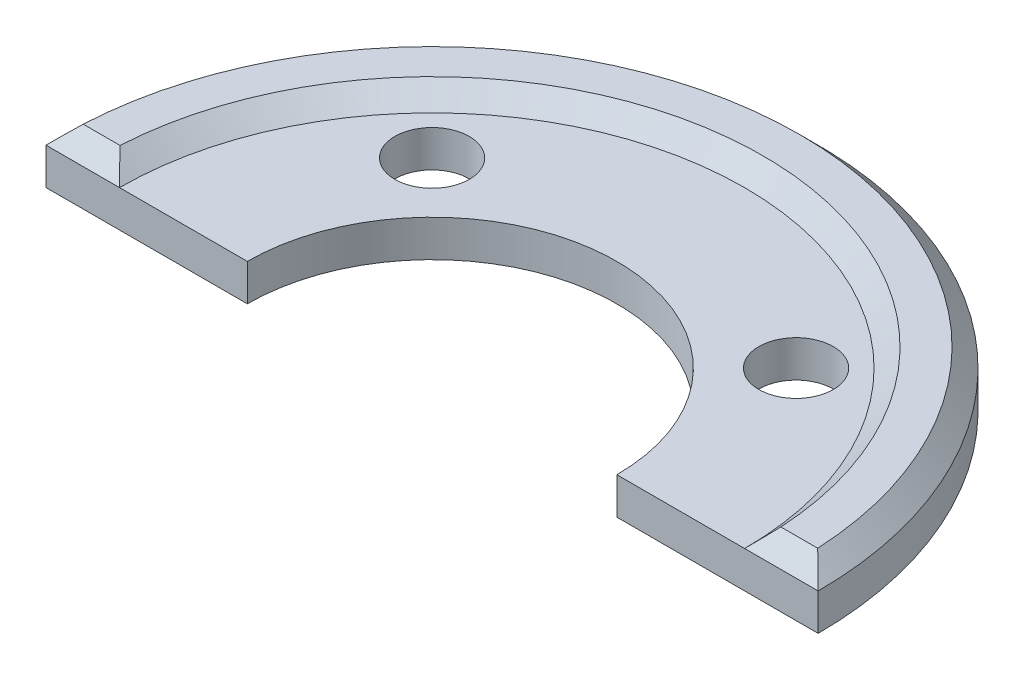
SolidWorks part; units mm, degrees
material "ABS"
ref_plane "正面" through (0, 0, 0) normal (0, 0, 1) x (1, 0, 0)
ref_plane "平面" through (0, 0, 0) normal (0, 1, 0) x (1, 0, 0)
ref_plane "右側面" through (0, 0, 0) normal (1, 0, 0) x (0, 0, -1)
sketch "ｽｹｯﾁ1" plane through (0, 0, 0) normal (0, 1, 0) x (1, 0, 0)
  line L0 (-10.05, 0) -> (-39, 0)
  line L1 (-39, 0) -> (-47.5, 8.5)
  line L2 (-47.5, 8.5) -> (-47.5, 58)
  line L3 (-47.5, 58) -> (47.5, 58)
  line L4 (47.5, 58) -> (47.5, 8.5)
  line L5 (47.5, 8.5) -> (39, 0)
  line L6 (39, 0) -> (10.05, 0)
  line L7 (-10.05, 0) -> (0, 0) construction
  line L8 (0, 0) -> (10.05, 0) construction
  arc A0 (10.05, 0) -> (-10.05, 0) centre (0, 0) ccw
  dimension "D1" = 20.1
  dimension "D2" = 95
  dimension "D3" = 58
  dimension "D4" = 78
extrude "ﾎﾞｽ - 押し出し1" add sketch "ｽｹｯﾁ1" along normal blind 3
hole_wizard "M2 なべ頭ねじ用座ぐり穴1" positions "ｽｹｯﾁ2" profile "ｽｹｯﾁ3" counterbore size "M2" standard "ISO"
sketch "ｽｹｯﾁ2" plane through (0, 3, 0) normal (0, 1, 0) x (1, 0, 0)
  line L0 (-43.5, 54) -> (-22.5, 54) construction
  line L2 (47.5, 58) -> (-47.5, 58) construction
  line L3 (-47.5, 58) -> (-47.5, 8.5) construction
  point P0 (-43.5, 54)
  point P2 (-22.5, 54)
  dimension "D1" = 4
  dimension "D2" = 4
  dimension "D3" = 21
sketch "ｽｹｯﾁ3" plane through (-43.5, 3, -54) normal (1, 0, 0) x (0, 0, 1)
  line L0 (0, 0) -> (0, 4.6309)
  line L1 (0, 4.6309) -> (1.05, 4)
  line L2 (1.05, 4) -> (1.05, 1)
  line L3 (1.05, 1) -> (2, 1)
  line L4 (2, 1) -> (2, 0)
  line L5 (2, 0) -> (0, 0)
  line L10 (0, 4.6309) -> (-1.05, 4) construction
  line L11 (0, -6.35) -> (0, 107.95) construction
  dimension "穴の直径" = 2.1
  dimension "穴の深さ" = 4
  dimension "座ぐり穴の直径" = 4
  dimension "座ぐり穴の深さ" = 1
  dimension "ﾄﾞﾘﾙ角度" = 118
pattern_linear "直線ﾊﾟﾀｰﾝ1" count 3 spacing 33 along (1, 0, 0) of "M2 なべ頭ねじ用座ぐり穴1"
pattern_linear "直線ﾊﾟﾀｰﾝ2" count 3 spacing 10.5 along (0, 0, 1) of "M2 なべ頭ねじ用座ぐり穴1", "直線ﾊﾟﾀｰﾝ1"
pattern_linear "直線ﾊﾟﾀｰﾝ3" count 2 spacing 31.5 along (0, 0, 1) of "M2 なべ頭ねじ用座ぐり穴1"
hole_wizard "M2 ねじ穴1" positions "ｽｹｯﾁ4" profile "ｽｹｯﾁ5" tap size "M2" standard "ISO"
sketch "ｽｹｯﾁ4" plane through (0, 3, 0) normal (0, 1, 0) x (1, 0, 0)
  line L0 (-22.5, 10.5) -> (-22.5, 22.5) construction
  line L1 (-22.5, 22.5) -> (-10.5, 22.5) construction
  line L2 (-10.5, 22.5) -> (-10.5, 33) construction
  line L4 (-39, 0) -> (-10.05, 0) construction
  point P0 (-10.5, 22.5)
  point P2 (-22.5, 10.5)
  dimension "D1" = 10.5
sketch "ｽｹｯﾁ5" plane through (-10.5, 3, -22.5) normal (1, 0, 0) x (0, 0, 1)
  line L0 (0, 0) -> (0, 6.4807)
  line L1 (0, 6.4807) -> (0.8, 6)
  line L2 (0.8, 6) -> (0.8, 0)
  line L5 (0.8, 0) -> (0, 0)
  line L10 (0, 6.4807) -> (-0.8, 6) construction
  line L11 (0, -6.35) -> (0, 107.95) construction
  dimension "ねじ下穴ﾄﾞﾘﾙ直径" = 1.6
  dimension "ねじ下穴ﾄﾞﾘﾙの深さ" = 6
  dimension "ﾄﾞﾘﾙ角度" = 118
cosmetic thread "穴のねじ山1" parameters "D1"=4, "D2"=2
cosmetic thread "穴のねじ山2" parameters "D1"=4, "D2"=2
hole_wizard "M2 なべ頭ねじ用座ぐり穴2" positions "ｽｹｯﾁ6" profile "ｽｹｯﾁ7" counterbore size "M2" standard "ISO"
sketch "ｽｹｯﾁ6" plane through (0, 3, 0) normal (0, 1, 0) x (1, 0, 0)
  line L0 (-43.5, 22.5) -> (-43.5, 12) construction
  line L3 (-43.5, 33) -> (-43.5, 22.5) construction
  point P0 (-43.5, 12)
sketch "ｽｹｯﾁ7" plane through (-43.5, 3, -12) normal (1, 0, 0) x (0, 0, 1)
  line L0 (0, 0) -> (0, 6.6309)
  line L1 (0, 6.6309) -> (1.05, 6)
  line L2 (1.05, 6) -> (1.05, 1)
  line L3 (1.05, 1) -> (2, 1)
  line L4 (2, 1) -> (2, 0)
  line L5 (2, 0) -> (0, 0)
  line L10 (0, 6.6309) -> (-1.05, 6) construction
  line L11 (0, -6.35) -> (0, 107.95) construction
  dimension "穴の直径" = 2.1
  dimension "穴の深さ" = 6
  dimension "座ぐり穴の直径" = 4
  dimension "座ぐり穴の深さ" = 1
  dimension "ﾄﾞﾘﾙ角度" = 118
mirror "ﾐﾗｰ1" about plane through (0, 0, 0) normal (1, 0, 0) of "M2 なべ頭ねじ用座ぐり穴2", "M2 ねじ穴1", "直線ﾊﾟﾀｰﾝ3"
cosmetic thread "穴のねじ山3" parameters "D1"=4, "D2"=2
cosmetic thread "穴のねじ山4" parameters "D1"=4, "D2"=2
sketch "ｽｹｯﾁ8" plane through (0, 3, 0) normal (0, 1, 0) x (1, 0, 0)
  circle A0 centre (0, 0) radius 17
  dimension "D1" = 34
extrude "ｶｯﾄ - 押し出し1" cut sketch "ｽｹｯﾁ8" against normal blind 1
sketch "ｽｹｯﾁ9" plane through (0, 2, 0) normal (0, 1, 0) x (1, 0, 0)
  line L0 (-9.8995, 9.8995) -> (0, 0) construction
  line L2 (-17, 0) -> (-10.05, 0) construction
  circle A0 centre (-9.8995, 9.8995) radius 2.025
  dimension "D1" = 4.05
  dimension "D2" = 45
  dimension "D3" = 14
extrude "ｶｯﾄ - 押し出し2" cut sketch "ｽｹｯﾁ9" against normal through all
pattern_circular "円形ﾊﾟﾀｰﾝ1" count 2 every 90 about axis through (0, 3, 0) along (0, -1, 0) of "ｶｯﾄ - 押し出し2"
fillet "ﾌｨﾚｯﾄ1" radius 4 6 edges at (-47.5, 1.5, -8.5) (-39, 1.5, 0) (39, 1.5, 0) (47.5, 1.5, -8.5) (47.5, 1.5, -58) (-47.5, 1.5, -58)
sketch "ｽｹｯﾁ10" plane through (0, 3, 0) normal (0, 1, 0) x (1, 0, 0)
  line L0 (17, 0) -> (37.3431, 0) construction
  line L1 (-47.5, 0) -> (-21, 0)
  line L2 (-47.5, 0) -> (-47.5, 58)
  line L3 (-47.5, 58) -> (47.5, 58)
  line L4 (47.5, 0) -> (47.5, 58)
  line L5 (-47.5, 0) -> (47.5, 58) construction
  line L6 (-47.5, 58) -> (47.5, 0) construction
  line L7 (43.5, 58) -> (-43.5, 58) construction
  line L8 (-47.5, 54) -> (-47.5, 10.1569) construction
  line L9 (47.5, 10.1569) -> (47.5, 54) construction
  line L10 (21, 0) -> (47.5, 0)
  arc A0 (21, 0) -> (-21, 0) centre (0, 0) ccw
  point P7 (0, 29)
  dimension "D1" = 42
extrude "ｶｯﾄ - 押し出し3" cut sketch "ｽｹｯﾁ10" against normal through all
chamfer "面取り2" distance 1 angle 45 4 edges at (19, 3, 0) (0, 3, -17) (-19, 3, 0) (0, 3, -21)
